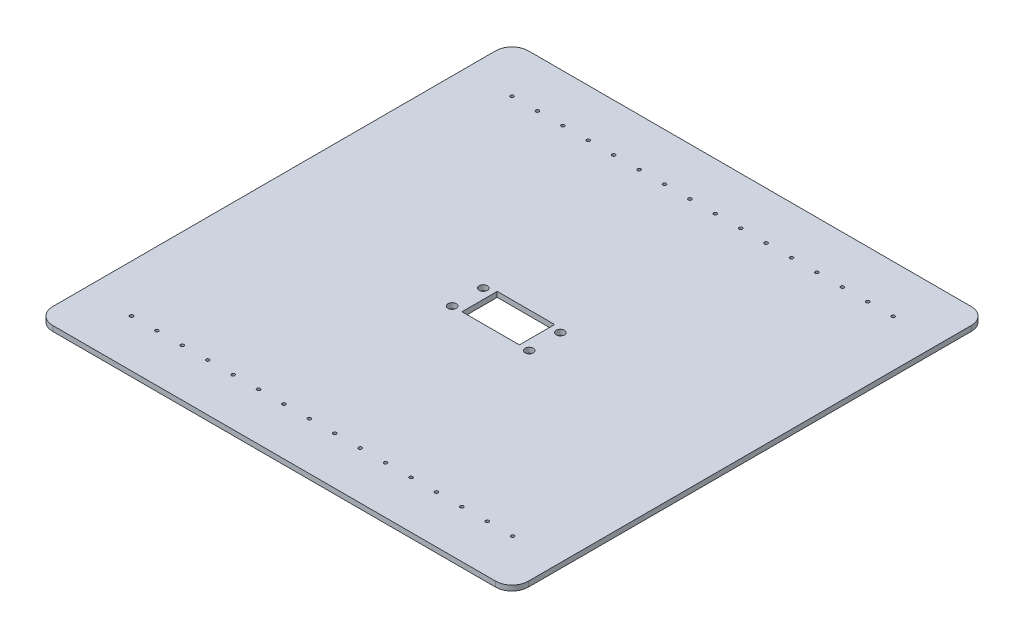
SolidWorks part; units mm, degrees
ref_plane "Front Plane" through (0, 0, 0) normal (0, 0, 1) x (1, 0, 0)
ref_plane "Top Plane" through (0, 0, 0) normal (0, 1, 0) x (1, 0, 0)
ref_plane "Right Plane" through (0, 0, 0) normal (1, 0, 0) x (0, 0, -1)
sketch "Sketch1" plane through (0, 0, 0) normal (0, 1, 0) x (1, 0, 0)
  line L0 (-145, 116) -> (145, 116) construction
  line L1 (145, -145) -> (-145, -145)
  line L2 (145, -145) -> (145, 145)
  line L3 (145, 145) -> (-145, 145)
  line L4 (-145, -145) -> (-145, 145)
  line L5 (145, -145) -> (-145, 145) construction
  line L6 (145, 145) -> (-145, -145) construction
  line L7 (-145, 87) -> (145, 87) construction
  line L8 (-145, 58) -> (145, 58) construction
  line L9 (-145, 29) -> (145, 29) construction
  line L10 (-145, 0) -> (145, 0) construction
  line L11 (-145, -29) -> (145, -29) construction
  line L12 (-145, -58) -> (145, -58) construction
  line L13 (-145, -87) -> (145, -87) construction
  line L14 (-145, -116) -> (145, -116) construction
  line L15 (-145, -145) -> (145, -145) construction
  point P0 (0, 0)
  dimension "D1" = 290
  dimension "D2" = 290
  dimension "D3" = 29
  dimension "D5" = 29
  dimension "D4" = 10
extrude "Base Plate" add sketch "Sketch1" along normal blind 3.175
hole_wizard "Caster Holes" positions "Sketch2" profile "Sketch3" hole size "Ø2.0" standard "ANSI Metric" end condition through all
sketch "Sketch2" plane through (0, 3.175, 0) normal (0, 1, 0) x (1, 0, 0)
  line L0 (-145, 116) -> (145, 116) construction
  line L2 (145, -145) -> (-145, 145) construction
  line L3 (-1.7463, 0) -> (1.7463, 0) construction
  line L4 (-145, -116) -> (145, -116) construction
  point P0 (-116, 116)
  point P8 (-100.506, 116)
  point P14 (-116, 116)
  point P24 (-85.012, 116)
  point P25 (-69.518, 116)
  point P26 (-54.024, 116)
  point P27 (-38.53, 116)
  point P28 (-23.036, 116)
  point P29 (-7.542, 116)
  point P30 (7.952, 116)
  point P31 (23.446, 116)
  point P32 (38.94, 116)
  point P33 (54.434, 116)
  point P34 (69.928, 116)
  point P35 (85.422, 116)
  point P36 (100.916, 116)
  point P37 (116.41, 116)
  point P40 (116.41, -116)
  point P41 (100.916, -116)
  point P42 (85.422, -116)
  point P43 (69.928, -116)
  point P44 (54.434, -116)
  point P45 (38.94, -116)
  point P46 (23.446, -116)
  point P47 (7.952, -116)
  point P48 (-7.542, -116)
  point P49 (-23.036, -116)
  point P50 (-38.53, -116)
  point P51 (-54.024, -116)
  point P52 (-69.518, -116)
  point P53 (-85.012, -116)
  point P54 (-100.506, -116)
  point P55 (-116, -116)
  point P56 (-23.036, -116)
  dimension "D1" = 15.494
  dimension "D3" = 15.494
  dimension "D2" = 15
sketch "Sketch3" plane through (-116, 3.175, -116) normal (1, 0, 0) x (0, 0, 1)
  line L0 (0, 0) -> (0, 3.175)
  line L1 (0, 3.175) -> (1, 3.175)
  line L2 (1, 3.175) -> (1, 0)
  line L5 (1, 0) -> (0, 0)
  line L11 (0, -6.35) -> (0, 107.95) construction
  dimension "Thru Hole Dia." = 2
  dimension "Thru Hole Depth" = 3.175
fillet "Fillet1" radius 10 4 edges at (145, 1.5875, 145) (-145, 1.5875, 145) (145, 1.5875, -145) (-145, 1.5875, -145)
sketch "Sketch4" plane through (0, 0, 0) normal (0, -1, 0) x (1, 0, 0)
  line L0 (145, 0) -> (-145, 0) construction
  line L1 (-145, -135) -> (-145, 135) construction
  line L2 (0, -145) -> (0, 145) construction
  line L3 (-135, 145) -> (135, 145) construction
  point P6 (0, 0)
  point P12 (0, 0)
sketch "Sketch5" plane through (0, 3.175, 0) normal (0, 1, 0) x (1, 0, 0)
  line L0 (0, 145) -> (0, -145) construction
  line L1 (145, 0) -> (-145, 0) construction
  line L2 (0, 145) -> (0, -145) construction
  line L4 (-17.5, -13) -> (17.5, -13)
  line L5 (-17.5, -13) -> (-17.5, 8.5)
  line L6 (-17.5, 8.5) -> (17.5, 8.5)
  line L7 (17.5, -13) -> (17.5, 8.5)
  line L8 (-17.5, -13) -> (17.5, 8.5) construction
  line L9 (-17.5, 8.5) -> (17.5, -13) construction
  circle A0 centre (-23.5, 6) radius 2.5
  circle A2 centre (-23.5, -13) radius 2.5
  circle A3 centre (23.5, 6) radius 2.5
  circle A4 centre (23.5, -13) radius 2.5
  point P2 (1.1063, -15.7734)
  point P13 (0, -2.25)
  dimension "D1" = 5
  dimension "D2" = 23.5
  dimension "D3" = 6
  dimension "D4" = 19
  dimension "D5" = 6
  dimension "D6" = 6
extrude "Reflect Holes" cut sketch "Sketch5" against normal up to surface (3.175 mm away) up to face at (-100.506, 0, -115)
